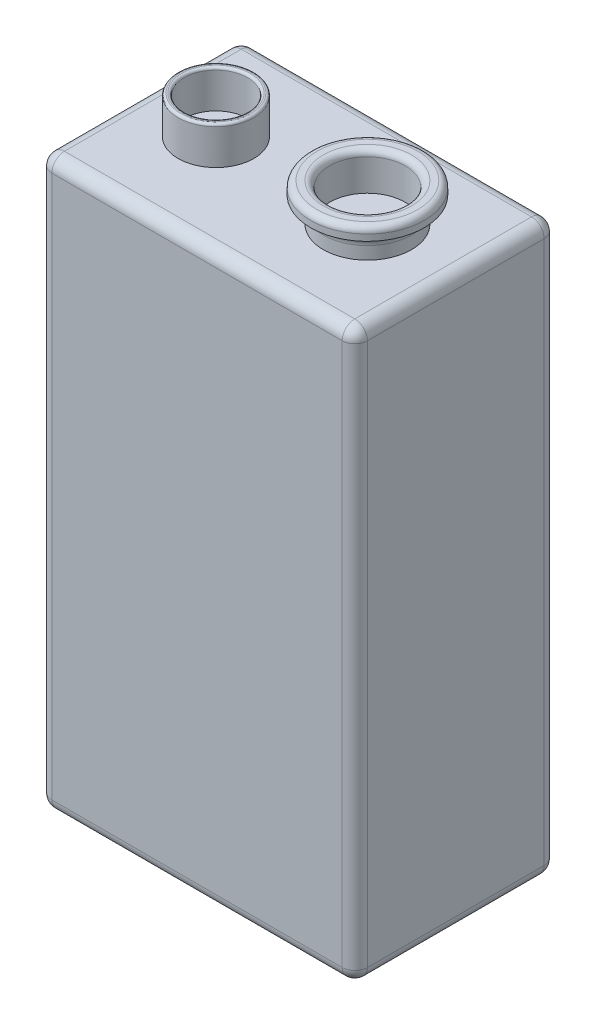
SolidWorks part; units mm, degrees
ref_plane "Front Plane" through (0, 0, 0) normal (0, 0, 1) x (1, 0, 0)
ref_plane "Top Plane" through (0, 0, 0) normal (0, 1, 0) x (1, 0, 0)
ref_plane "Right Plane" through (0, 0, 0) normal (1, 0, 0) x (0, 0, -1)
sketch "Sketch1" plane through (0, 0, 0) normal (0, 1, 0) x (1, 0, 0)
  line L1 (12.5, 8) -> (-12.5, 8)
  line L2 (12.5, 8) -> (12.5, -8)
  line L3 (12.5, -8) -> (-12.5, -8)
  line L4 (-12.5, 8) -> (-12.5, -8)
  line L5 (12.5, 8) -> (-12.5, -8) construction
  line L6 (12.5, -8) -> (-12.5, 8) construction
  point P0 (0, 0)
  dimension "D1" = 25
  dimension "D2" = 16
extrude "Boss-Extrude1" add sketch "Sketch1" along normal blind 45
fillet "Fillet1" radius 1 12 edges at (0, 0, 8) (12.5, 0, 0) (0, 0, -8) (-12.5, 0, 0) (0, 45, -8) (12.5, 45, 0) (0, 45, 8) (-12.5, 45, 0) (-12.5, 22.5, -8) (12.5, 22.5, -8) (-12.5, 22.5, 8) (12.5, 22.5, 8)
sketch "Sketch2" plane through (0, 45, 0) normal (0, 1, 0) x (1, 0, 0)
  line L0 (-12.5, -7) -> (-12.5, 7) construction
  circle A0 centre (-6.5, 0) radius 3
  circle A1 centre (-6.5, 0) radius 2.5
  point P3 (-12.5, 0)
  dimension "D1" = 6
  dimension "D2" = 5
  dimension "D3" = 6
extrude "Boss-Extrude2" add sketch "Sketch2" along normal blind 3
sketch "Sketch3" plane through (0, 45, 0) normal (0, 1, 0) x (1, 0, 0)
  line L0 (11.5, -7) -> (11.5, 7) construction
  circle A0 centre (5.5, 0) radius 3.5
  circle A1 centre (5.5, 0) radius 3
  point P3 (11.5, 0)
  dimension "D1" = 7
  dimension "D2" = 6
  dimension "D3" = 6
extrude "Boss-Extrude3" add sketch "Sketch3" along normal blind 2
sketch "Sketch4" plane through (0, 47, 0) normal (0, 1, 0) x (1, 0, 0)
  circle A0 centre (5.5, 0) radius 3
  circle A1 centre (5.5, 0) radius 4.5
  dimension "D1" = 9
extrude "Boss-Extrude4" add sketch "Sketch4" along normal blind 1
fillet "Fillet4" radius 1 1 edges at (5.5, 47, 3.5)
fillet "Fillet5" radius 0.5 2 edges at (5.5, 48, 3) (5.5, 48, 4.5)
fillet "Fillet6" radius 0.2 2 edges at (-6.5, 48, 2.5) (-6.5, 48, 3)
